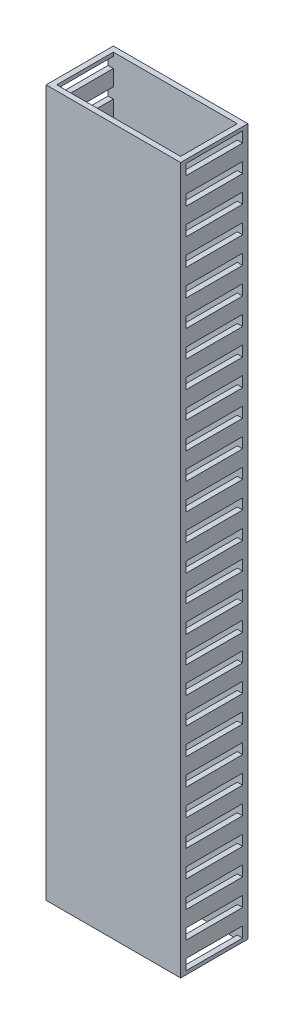
SolidWorks part; units mm, degrees
ref_plane "Front Plane" through (0, 0, 0) normal (0, 0, 1) x (1, 0, 0)
ref_plane "Top Plane" through (0, 0, 0) normal (0, 1, 0) x (1, 0, 0)
ref_plane "Right Plane" through (0, 0, 0) normal (1, 0, 0) x (0, 0, -1)
sketch "Sketch1" plane through (0, 0, 0) normal (0, 1, 0) x (1, 0, 0)
  line L0 (0, 25.4) -> (50.8, 0) construction
  line L1 (0, 0) -> (50.8, 0)
  line L2 (0, 0) -> (0, 25.4)
  line L3 (0, 25.4) -> (50.8, 25.4)
  line L4 (50.8, 0) -> (50.8, 25.4)
  line L6 (2, 23.4) -> (48.8, 23.4)
  line L7 (2, 23.4) -> (2, 2)
  line L8 (2, 2) -> (48.8, 2)
  line L9 (48.8, 23.4) -> (48.8, 2)
  line L10 (2, 23.4) -> (48.8, 2) construction
  line L11 (2, 2) -> (48.8, 23.4) construction
  point P5 (25.4, 12.7)
  dimension "D1" = 50.8
  dimension "D2" = 25.4
  dimension "D3" = 2
  dimension "D4" = 2
extrude "Boss-Extrude1" add sketch "Sketch1" against normal offset from surface (266.7 mm away) 25.4
sketch "Sketch2" plane through (50.8, 0, 0) normal (1, 0, 0) x (0, 0, -1)
  line L0 (2, -266.7) -> (2, 0) construction
  line L1 (2, -266.7) -> (2, 0)
  line L2 (23.4, -266.7) -> (23.4, 0) construction
  line L3 (23.4, -266.7) -> (23.4, 0)
  line L4 (23.4, -133.35) -> (2, -133.35) construction
  line L6 (2, -131.35) -> (23.4, -131.35)
  line L7 (2, -131.35) -> (2, -135.35)
  line L8 (2, -135.35) -> (23.4, -135.35)
  line L9 (23.4, -131.35) -> (23.4, -135.35)
  line L10 (2, -131.35) -> (23.4, -135.35) construction
  line L11 (2, -135.35) -> (23.4, -131.35) construction
  point P6 (12.7, -133.35)
  dimension "D1" = 4
extrude "Cut-Extrude1" cut sketch "Sketch2" against normal through all contours L1 L8 L3 L6 region at (50.8, -133.35, -12.7)
pattern_linear "LPattern1" count 14 spacing 10 along (0, 1, 0) count 14 spacing 10 along (0, -1, 0) of "Cut-Extrude1"
